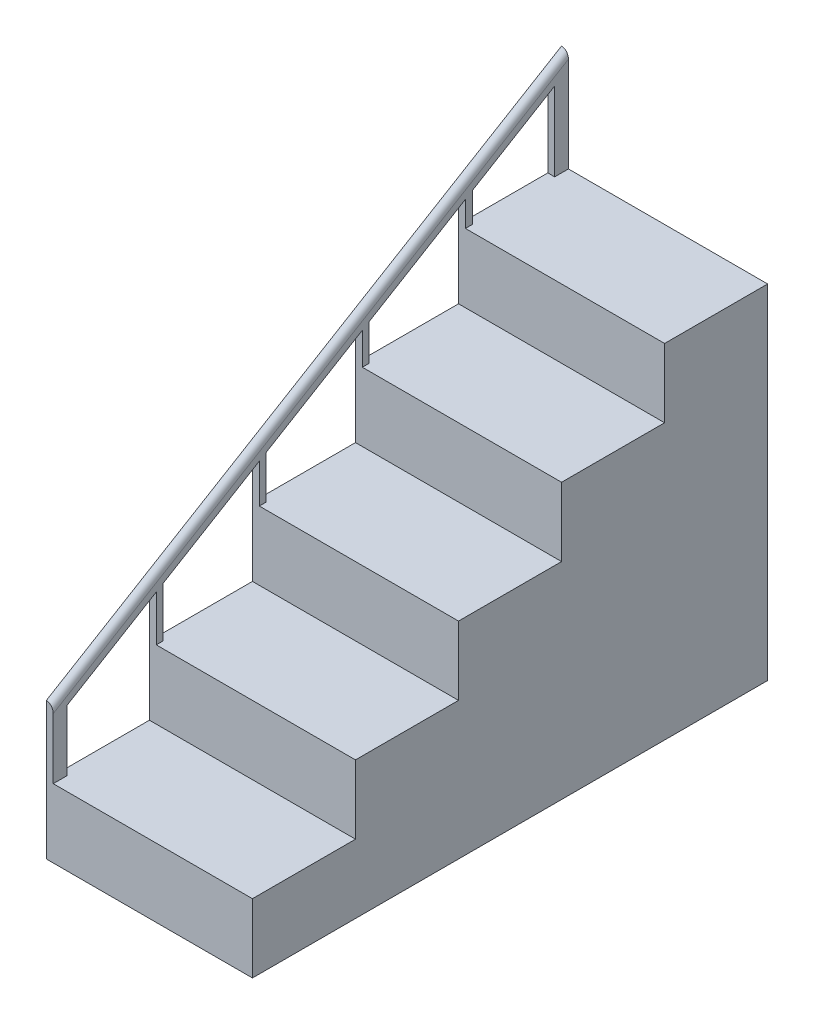
SolidWorks part; units mm, degrees
ref_plane "Front Plane" through (0, 0, 0) normal (0, 0, 1) x (1, 0, 0)
ref_plane "Top Plane" through (0, 0, 0) normal (0, 1, 0) x (1, 0, 0)
ref_plane "Right Plane" through (0, 0, 0) normal (1, 0, 0) x (0, 0, -1)
sketch "Sketch1" plane through (0, 0, 0) normal (1, 0, 0) x (0, 0, -1)
  line L0 (0, 0) -> (0, 100)
  line L1 (0, 100) -> (150, 100)
  line L2 (150, 100) -> (150, 200)
  line L3 (150, 200) -> (300, 200)
  line L4 (300, 200) -> (300, 300)
  line L5 (300, 300) -> (450, 300)
  line L6 (450, 300) -> (450, 400)
  line L7 (450, 400) -> (600, 400)
  line L8 (600, 400) -> (600, 500)
  line L9 (600, 500) -> (750, 500)
  line L10 (750, 500) -> (750, 0)
  line L11 (750, 0) -> (0, 0)
  dimension "D1" = 100
  dimension "D2" = 150
  dimension "D3" = 100
  dimension "D4" = 150
  dimension "D5" = 100
  dimension "D6" = 150
  dimension "D7" = 100
  dimension "D8" = 150
  dimension "D9" = 100
  dimension "D10" = 150
extrude "Boss-Extrude1" add sketch "Sketch1" along normal blind 300
sketch "Sketch5" plane through (0, 0, 0) normal (-1, 0, 0) x (0, 0, 1)
  line L0 (-750, 500) -> (-750, 650)
  line L1 (0, 100) -> (0, 200)
  line L2 (-750, 650) -> (0, 200)
  line L3 (-730, 500) -> (-730, 614.6762)
  line L4 (-730, 614.6762) -> (-20, 188.6762)
  line L5 (-20, 100) -> (-20, 188.6762)
  line L6 (-750, 500) -> (-730, 500)
  line L7 (-20, 100) -> (0, 100)
  dimension "D1" = 150
  dimension "D2" = 100
  dimension "D3" = 20
extrude "Boss-Extrude4" add sketch "Sketch5" against normal blind 10
sketch "Sketch8" plane through (0, 0, 0) normal (-1, 0, 0) x (0, 0, 1)
  line L0 (-600, 500) -> (-600, 536.6762)
  line L1 (-730, 614.6762) -> (-20, 188.6762) construction
  line L2 (-450, 400) -> (-450, 446.6762)
  line L3 (-300, 300) -> (-300, 356.6762)
  line L4 (-150, 200) -> (-150, 266.6762)
  line L5 (-610, 500) -> (-610, 536.6762)
  line L6 (-460, 400) -> (-460, 446.6762)
  line L7 (-310, 300) -> (-310, 356.6762)
  line L8 (-160, 200) -> (-160, 266.6762)
  line L9 (-610, 536.6762) -> (-610, 542.6762)
  line L10 (-610, 542.6762) -> (-600, 536.6762)
  line L11 (-610, 500) -> (-600, 500)
  line L12 (-460, 446.6762) -> (-460, 452.6762)
  line L13 (-460, 452.6762) -> (-450, 446.6762)
  line L14 (-460, 400) -> (-450, 400)
  line L15 (-310, 356.6762) -> (-310, 362.6762)
  line L16 (-310, 362.6762) -> (-300, 356.6762)
  line L17 (-310, 300) -> (-300, 300)
  line L18 (-160, 266.6762) -> (-160, 272.6762)
  line L19 (-160, 272.6762) -> (-150, 266.6762)
  line L20 (-160, 200) -> (-150, 200)
  dimension "D1" = 10
  dimension "D2" = 10
  dimension "D3" = 10
  dimension "D4" = 10
extrude "Boss-Extrude5" add sketch "Sketch8" against normal blind 10
fillet "Fillet1" radius 10 1 edges at (10, 425, -375)
